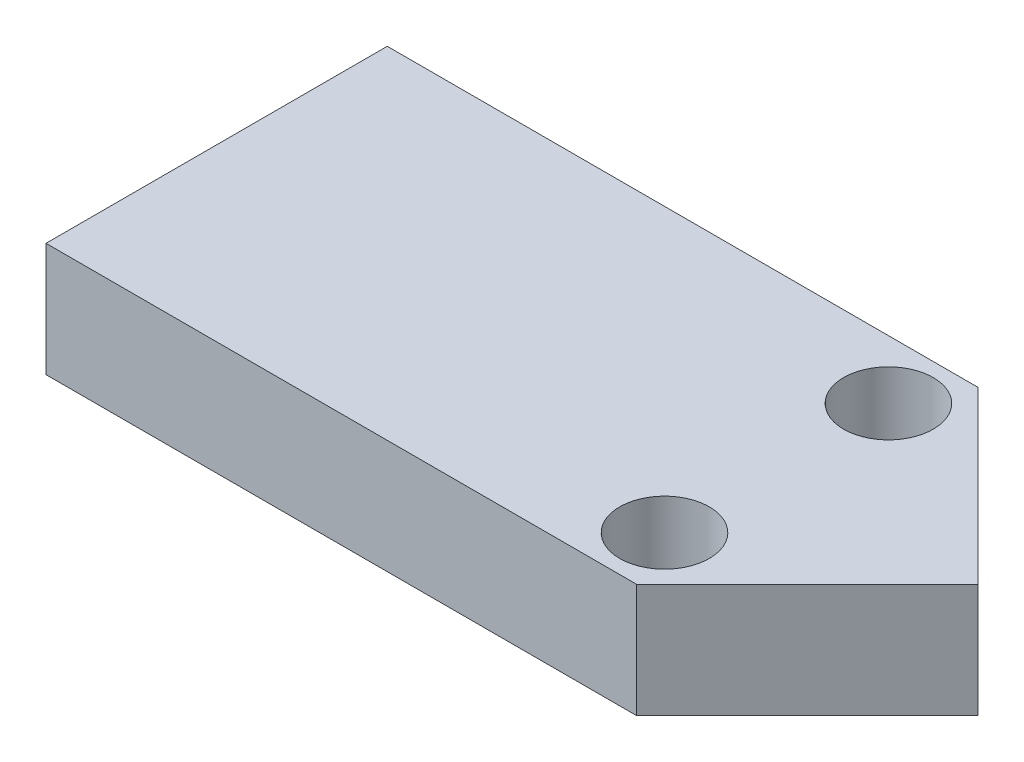
SolidWorks part; units mm, degrees
ref_plane "Front Plane" through (0, 0, 0) normal (0, 0, 1) x (1, 0, 0)
ref_plane "Top Plane" through (0, 0, 0) normal (0, 1, 0) x (1, 0, 0)
ref_plane "Right Plane" through (0, 0, 0) normal (1, 0, 0) x (0, 0, -1)
sketch "Sketch1" plane through (0, 0, 0) normal (0, 1, 0) x (1, 0, 0)
  line L0 (131.9, 76.2) -> (170, 38.1)
  line L1 (0, 0) -> (131.9, 0)
  line L2 (0, 0) -> (0, 76.2)
  line L3 (0, 76.2) -> (131.9, 76.2)
  line L4 (131.9, 0) -> (131.9, 76.2)
  line L5 (170, 38.1) -> (131.9, 0)
  line L6 (0, 38.1) -> (170, 38.1)
  dimension "D1" = 76.2
  dimension "D2" = 170
extrude "Boss-Extrude1" add sketch "Sketch1" along normal blind 25.4 contours L6 L2 L1 L4 | L6 L4 L5 | L4 L6 L0 | L2 L6 L4 L3 region at (65.95, 0, -57.15) region at (144.6, 0, -50.8) region at (144.6, 0, -25.4) region at (65.95, 0, -19.05)
sketch "Sketch2" plane through (0, 25.4, 0) normal (0, 1, 0) x (1, 0, 0)
  line L0 (170, 38.1) -> (125, 38.1)
  line L1 (125, 38.1) -> (125, 13.1)
  line L2 (125, 38.1) -> (125, 63.1)
  circle A0 centre (125, 63.1) radius 10
  circle A1 centre (125, 13.1) radius 10
  dimension "D1" = 45
  dimension "D2" = 25
  dimension "D3" = 25
extrude "Cut-Extrude1" cut sketch "Sketch2" against normal blind 25.4 contours A0 | A1
